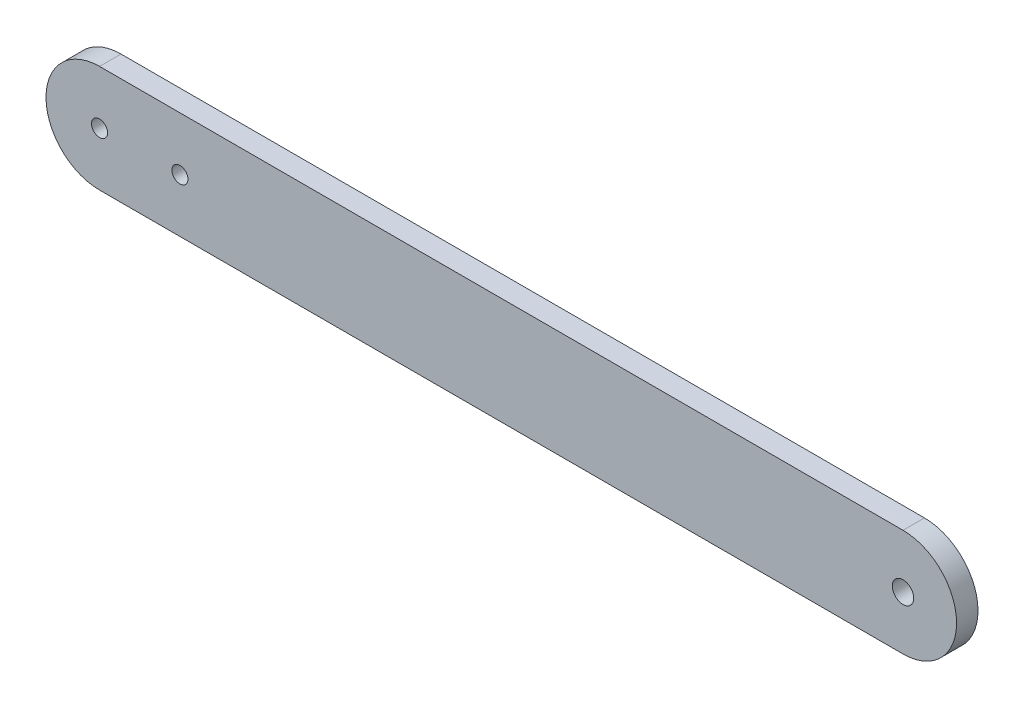
SolidWorks part; units mm, degrees
ref_plane "Plan de face" through (0, 0, 0) normal (0, 0, 1) x (1, 0, 0)
ref_plane "Plan de dessus" through (0, 0, 0) normal (0, 1, 0) x (1, 0, 0)
ref_plane "Plan de droite" through (0, 0, 0) normal (1, 0, 0) x (0, 0, -1)
sketch "Esquisse1" plane through (0, 0, 0) normal (0, 0, 1) x (1, 0, 0)
  line L0 (0, 10) -> (-170, 10) construction
  line L1 (0, 0) -> (-170, 0)
  line L2 (0, 0) -> (0, 20)
  line L3 (0, 20) -> (-170, 20)
  line L4 (-170, 0) -> (-170, 20)
  circle A0 centre (-160, 10) radius 1.5
  circle A1 centre (-10, 10) radius 2
  circle A2 centre (-145, 10) radius 1.5
  dimension "D1" = 10
  dimension "D2" = 10
  dimension "D4" = 3
  dimension "D6" = 15
  dimension "D7" = 3
  dimension "D8" = 4
  dimension "D3" = 20
  dimension "D5" = 170
extrude "Boss.-Extru.1" add sketch "Esquisse1" along normal blind 4
fillet "Congé1" 2 edges at (-170, 20, 2) (-170, 0, 2) type full round first side face at (-85, 20, 2) second side face at (-85, 0, 2) middle face at (-170, 10, 2)
fillet "Congé2" 2 edges at (0, 20, 2) (0, 0, 2) type full round first side face at (-80, 20, 2) second side face at (-80, 0, 2) middle face at (0, 10, 2)
